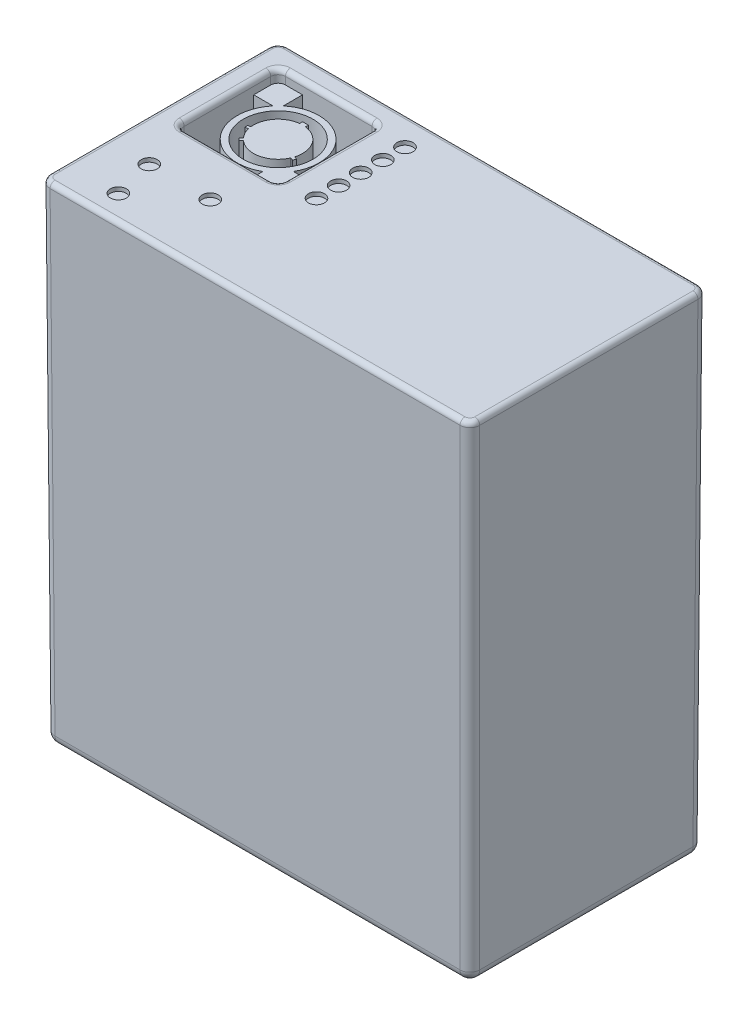
SolidWorks part; units mm, degrees
ref_plane "Front" through (0, 0, 0) normal (0, 0, 1) x (1, 0, 0)
ref_plane "Top" through (0, 0, 0) normal (0, 1, 0) x (1, 0, 0)
ref_plane "Right" through (0, 0, 0) normal (1, 0, 0) x (0, 0, -1)
sketch "Sketch1" plane through (0, 0, 0) normal (0, 1, 0) x (1, 0, 0)
  line L0 (-55.4863, 0) -> (55.4863, 0) construction
  line L1 (-55.4863, 30.7213) -> (55.4863, 30.7213)
  line L2 (-55.4863, 30.7213) -> (-55.4863, -30.7213)
  line L3 (-55.4863, -30.7213) -> (55.4863, -30.7213)
  line L4 (55.4863, 30.7213) -> (55.4863, -30.7213)
  dimension "D1" = 110.9726
  dimension "D2" = 61.4426
extrude "Extrude1" add sketch "Sketch1" against normal blind 126.238 draft 0.3
sketch "Sketch9" plane through (0, 0, 0) normal (0, 1, 0) x (1, 0, 0)
  line L0 (-55.4863, 30.7213) -> (-55.4863, -30.7213) construction
  line L1 (-25.2554, -1.4097) -> (-47.6172, -1.4097)
  line L2 (-23.3553, 0.4904) -> (-23.3553, 22.8522)
  line L3 (-25.2554, 24.7523) -> (-47.6172, 24.7523)
  line L4 (-49.5173, 0.4904) -> (-49.5173, 22.8522)
  line L5 (-23.3553, -1.4097) -> (-49.5173, 24.7523) construction
  line L6 (-23.3553, 24.7523) -> (-49.5173, -1.4097) construction
  line L7 (-43.2159, 24.7523) -> (-43.2159, 19.7968)
  line L8 (-44.5618, 18.4509) -> (-49.5173, 18.4509)
  line L9 (-36.4363, 11.6713) -> (-36.4363, 24.7523) construction
  line L10 (-45.7581, 20.9931) -> (-36.4363, 20.9931) construction
  line L11 (-27.8851, 2.3495) -> (-36.4363, 2.3495) construction
  line L12 (55.4863, 30.7213) -> (-55.4863, 30.7213) construction
  line L13 (-36.4363, 11.6713) -> (-23.3553, 11.6713) construction
  line L14 (-23.3553, 6.419) -> (-27.2493, 6.419)
  line L15 (-31.184, -1.4097) -> (-31.184, 2.4843)
  line L16 (-31.184, 2.4843) -> (-31.184, 6.419) construction
  line L17 (-31.184, 6.419) -> (-27.2493, 6.419) construction
  line L18 (-44.5618, 18.4509) -> (-43.2159, 18.4509) construction
  line L19 (-43.2159, 18.4509) -> (-43.2159, 19.7968) construction
  circle A0 centre (-36.4363, 11.6713) radius 10.5824
  arc A1 (-23.3553, 22.8522) -> (-25.2554, 24.7523) centre (-25.2554, 22.8522) ccw
  arc A2 (-25.2554, -1.4097) -> (-23.3553, 0.4904) centre (-25.2554, 0.4904) ccw
  arc A3 (-47.6172, -1.4097) -> (-49.5173, 0.4904) centre (-47.6172, 0.4904) cw
  arc A4 (-47.6172, 24.7523) -> (-49.5173, 22.8522) centre (-47.6172, 22.8522) ccw
  circle A5 centre (-45.7581, 20.9931) radius 1.7416
  circle A6 centre (-27.8851, 2.3495) radius 1.6493
  point P0 (-36.4363, 11.6713)
  dimension "D3" = 1.9001
  dimension "D6" = 18.6436
  dimension "D1" = 19.05
  dimension "D2" = 26.162
  dimension "D4" = 18.6436
  dimension "D5" = 19.05
extrude "Cut-Extrude1" cut sketch "Sketch9" against normal blind 3.175 contours L3 A4 L4 A3 L1 A2 L2 A1
extrude "Cut-Extrude2" cut sketch "Sketch9<3>" against normal blind 12.7 contours L2 A1 L3 L7 A0 L14 | A3 L1 L15 A0 L8 L4 region at (-39.4006, 0, 1.1394) region at (-25.3023, 0, -6.6893)
sketch "Sketch9<3>" plane through (0, 0, 0) normal (0, 1, 0) x (1, 0, 0) same geometry as "Sketch9"
sketch "Sketch10" plane through (0, -3.175, 0) normal (0, 1, 0) x (1, 0, 0)
  line L0 (-35.6743, 17.9754) -> (-35.6743, 18.7374)
  line L1 (-35.6743, 18.7374) -> (-37.1983, 18.7374)
  line L2 (-37.1983, 18.7374) -> (-37.1983, 17.9754)
  line L3 (-36.4363, 11.6713) -> (-42.6898, 10.5686) construction
  line L4 (-36.4363, 11.6713) -> (-40.9264, 7.1812) construction
  line L5 (-36.4363, 11.6713) -> (-30.4693, 9.4995) construction
  line L6 (-42.7447, 10.9458) -> (-43.5064, 10.8115)
  line L7 (-43.5064, 10.8115) -> (-43.3741, 10.0611)
  line L8 (-43.3741, 10.0611) -> (-42.6124, 10.1954)
  line L9 (-40.6489, 6.9199) -> (-41.1958, 6.3729)
  line L10 (-41.1958, 6.3729) -> (-41.7347, 6.9118)
  line L11 (-41.7347, 6.9118) -> (-41.1877, 7.4587)
  line L12 (-36.4363, 11.6713) -> (-36.4363, 18.7374) construction
  line L13 (-30.6103, 9.1454) -> (-29.8835, 8.8808)
  line L14 (-29.8835, 8.8808) -> (-29.6229, 9.5969)
  line L15 (-29.6229, 9.5969) -> (-30.3497, 9.8614)
  circle A0 centre (-36.4363, 11.6713) radius 6.35
  circle A1 centre (-36.4363, 11.6713) radius 8.9949
  arc A2 (-27.2493, 6.419) -> (-43.2159, 19.7968) centre (-36.4363, 11.6713) ccw construction
  dimension "D6" = 12.7
  dimension "D9" = 1.5875
  dimension "D1" = 0.762
  dimension "D2" = 0.762
  dimension "D3" = 100
  dimension "D4" = 1.524
  dimension "D5" = 0.762
  dimension "D7" = 135
  dimension "D8" = 110
extrude "Cut-Extrude3" cut sketch "Sketch10" against normal blind 12.7 contours A1 A0 L15 L14 L13 L9 L10 L11 L8 L7 L6 L2 L1 L0 region at (-45.1768, -3.175, -11.6713)
fillet "Fillet1" radius 2.54 8 edges at (0, -126.238, 30.0603) (54.8253, -126.238, 0) (0, -126.238, -30.0603) (-54.8253, -126.238, 0) (-55.1558, -63.119, -30.3908) (-55.1558, -63.119, 30.3908) (55.1558, -63.119, -30.3908) (55.1558, -63.119, 30.3908)
fillet "Fillet2" radius 1.27 16 edges at (54.7424, 0, -29.9774) (55.4863, 0, 0) (54.7424, 0, 29.9774) (0, 0, 30.7213) (-54.7424, 0, 29.9774) (-55.4863, 0, 0) (-54.7424, 0, -29.9774) (0, 0, -30.7213) (-36.4363, 0, -24.7523) (-48.9608, 0, -24.1958) (-49.5173, 0, -11.6713) (-48.9608, 0, 0.8532) (-36.4363, 0, 1.4097) (-23.9118, 0, 0.8532) (-23.3553, 0, -11.6713) (-23.9118, 0, -24.1958)
sketch "Sketch2" plane through (0, 0, 0) normal (0, 1, 0) x (1, 0, 0)
  line L0 (-36.4363, 11.6713) -> (-15.1003, 11.6713) construction
  line L4 (-44.3103, -13.7287) -> (-28.5623, -13.7287) construction
  circle A0 centre (-44.3103, -13.7287) radius 2.0701
  circle A1 centre (-28.5623, -13.7287) radius 2.0701
  circle A2 centre (-41.7703, -24.2443) radius 2.0701
  circle A3 centre (-15.1003, 23.1013) radius 2.0701
  circle A4 centre (-15.1003, 17.3863) radius 2.0701
  circle A5 centre (-15.1003, 11.6713) radius 2.0701
  circle A6 centre (-15.1003, 0.2413) radius 2.0701
  circle A7 centre (-15.1003, 5.9563) radius 2.0701
  dimension "D1" = 25.4
  dimension "D2" = 11.43
  dimension "D8" = 4.1402
  dimension "D3" = 5.715
  dimension "D4" = 21.336
  dimension "D5" = 7.874
  dimension "D6" = 35.9156
  dimension "D7" = 7.874
  dimension "D9" = 5.334
extrude "Extrude2" cut sketch "Sketch2" against normal blind 1.016
